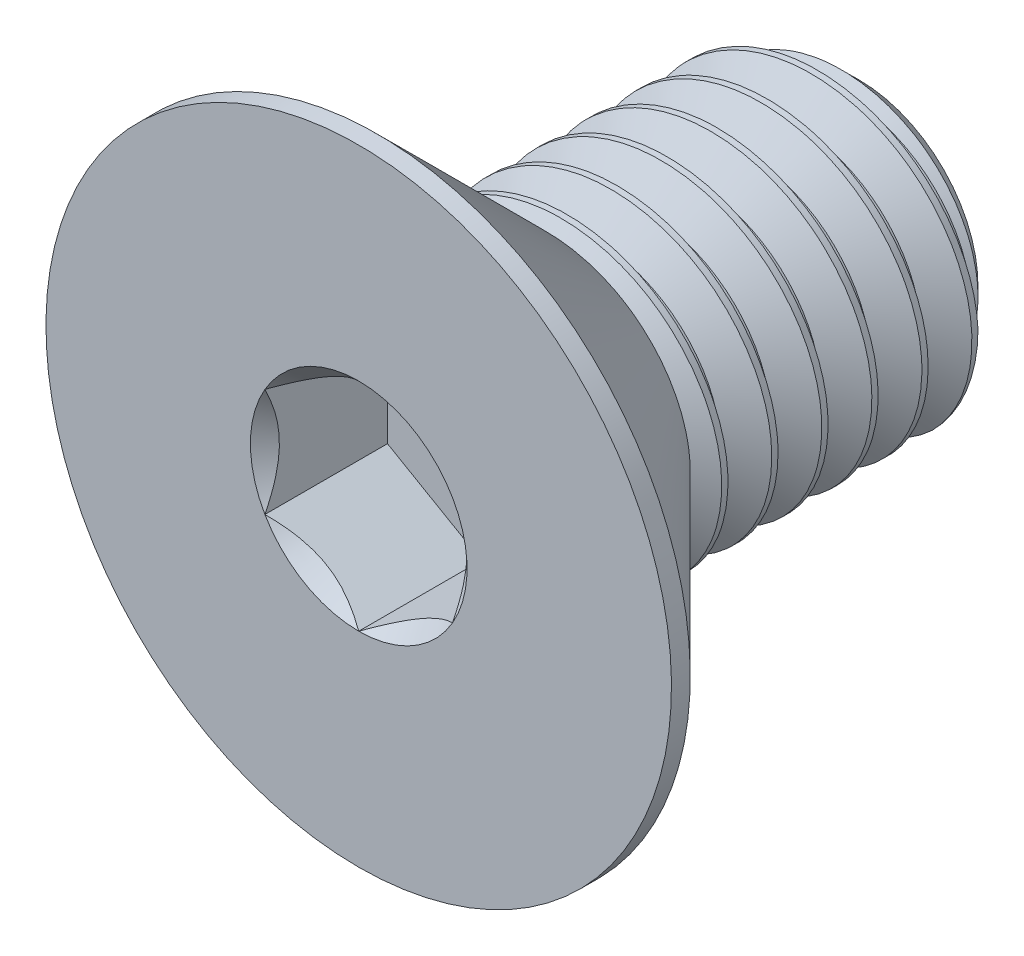
SolidWorks part; units mm, degrees
ref_plane "Front" through (0, 0, 0) normal (0, 0, 1) x (1, 0, 0)
ref_plane "Top" through (0, 0, 0) normal (0, 1, 0) x (1, 0, 0)
ref_plane "Right" through (0, 0, 0) normal (1, 0, 0) x (0, 0, -1)
sketch "Sketch1" plane through (0, 0, 0) normal (1, 0, 0) x (0, 0, -1)
  line L0 (0, 5) -> (0.3, 5) construction
  line L1 (0.3, 5) -> (2.8, 2.5) construction
  line L2 (0, 2.5) -> (8, 2.5)
  line L3 (8, 2.5) -> (8, 0)
  line L4 (8, 0) -> (0, 0)
  line L5 (0, 0) -> (0, 5) construction
  line L6 (0, 5) -> (0, -5) construction
  line L7 (8, 2.5) -> (8, -2.5) construction
  line L8 (0, -5) -> (0.3, -5) construction
  line L9 (0.3, -5) -> (2.8, -2.5) construction
  line L11 (0, 2.5) -> (0, 0)
  line L12 (2.8, 2.5) -> (2.8, 0) construction
revolve "Revolve1" add sketch "Sketch1" angle 360 mid plane about L4
sketch "Sketch3" plane through (0, 0, -8) normal (0, 0, -1) x (-1, 0, 0)
  circle A0 centre (0, 0) radius 2.5
curve "Helix/Spiral1" pitch 0.8 height 8 radius 2.5 centre (0, 0, -8) axis (0, 0, 1) start towards (0, 1, 0)
sketch "Sketch2" plane through (0, 0, 0) normal (1, 0, 0) x (0, 0, -1)
  line L0 (8, 2.5) -> (8.7, 2.5)
  line L1 (8.7, 2.5) -> (8.4, 1.9804)
  line L2 (8.4, 1.9804) -> (8.3, 1.9804)
  line L3 (8.3, 1.9804) -> (8, 2.5)
  line L4 (8.15, 2.2402) -> (8.55, 2.2402) construction
  dimension "D1" = 60
  dimension "D2" = 0.1
  dimension "D3" = 0.4
chamfer "Chamfer1" distance 0.6 angle 45 1 edges at (0, 2.5, -8)
sweep "Cut-Sweep1" cut profiles "Sketch2" path "Helix/Spiral1" align with end faces yes
sketch "Sketch7" plane through (0, 0, 0) normal (1, 0, 0) x (0, 0, -1)
  line L0 (0, 5) -> (0.3, 5) construction
  line L1 (0.3, 5) -> (2.8, 2.5) construction
  line L2 (0, 5) -> (0.3, 5)
  line L3 (0.3, 5) -> (2.8, 2.5)
  line L4 (2.8, 2.5) -> (2.8, 0) construction
  line L5 (2.8, 2.5) -> (2.8, 0)
  line L7 (0, 0) -> (0, 5) construction
  line L8 (0, 0) -> (0, 5)
  line L9 (0, 0) -> (2.8, 0)
  line L10 (5.5, 0) -> (-5.5, 0) construction
revolve "Revolve2" add sketch "Sketch7" angle 360 mid plane about L9
ref_plane "Plane1" through (0, 0, -2.8) normal (0, 0, 1) x (1, 0, 0)
sketch "Sketch8" plane through (0, 0, -2.8) normal (0, 0, 1) x (1, 0, 0)
  circle A0 centre (0, 0) radius 2.5
extrude "Boss-Extrude1" add sketch "Sketch8" against normal through all draft 45
sketch "Sketch5" plane through (0, 0, 0) normal (0, 0, 1) x (1, 0, 0)
  line L1 (1.5, -0.866) -> (1.5, 0.866)
  line L2 (1.5, 0.866) -> (0, 1.7321)
  line L3 (0, 1.7321) -> (-1.5, 0.866)
  line L4 (-1.5, 0.866) -> (-1.5, -0.866)
  line L5 (-1.5, -0.866) -> (0, -1.7321)
  line L6 (0, -1.7321) -> (1.5, -0.866)
  circle A0 centre (0, 0) radius 1.5 construction
  dimension "Hex" = 3
extrude "Cut-Extrude2" cut sketch "Sketch5" against normal blind 1.96
sketch "Sketch6" plane through (0, 0, 0) normal (0, 0, 1) x (1, 0, 0)
  circle A0 centre (0, 0) radius 1.7321
extrude "Cut-Extrude3" cut sketch "Sketch6" against normal blind 1.96 draft 45
sketch "Sketch9" [suppressed] plane through (0, 0, -5.5) normal (0, 0, 1) x (1, 0, 0)
  circle A1 centre (0, 0) radius 5
  circle A2 centre (0, 0) radius 5
  point P0 (0, 5)
  dimension "D1" = 0
extrude "Boss-Extrude2" [suppressed] add sketch "Sketch9" against normal offset from surface (18.5 mm away) 26 up to face at (0, 1.9, -8)
fillet "Fillet1" [suppressed] radius 0.5
sketch "Sketch10" plane through (0, 0, 0) normal (1, 0, 0) x (0, 0, -1)
  line L0 (8, 2.5) -> (8, -2.5) construction
  point P0 (6.8, -2.5)
  dimension "D1" = 1.2
equation "\"D3@Helix/Spiral1\" = \"Lg@Sketch1\""
equation "\"D2@Sketch2\" = \"D4@Helix/Spiral1\" * .125"
equation "\"D3@Sketch2\" = \"D4@Helix/Spiral1\" * .5"
equation "\"D1@Chamfer1\" = \"D4@Helix/Spiral1\" * .75"
equation "\"D1@Cut-Extrude2\" = \"Head Ht@Sketch1\" * .7"
equation "\"D1@Sketch10\" = \"D4@Helix/Spiral1\" * 1.5"
equation "\"D1@Cut-Extrude3\" = \"D1@Cut-Extrude2\""
equation "\"D1@Fillet1\" = \"Dia@Sketch1\" * .1"
